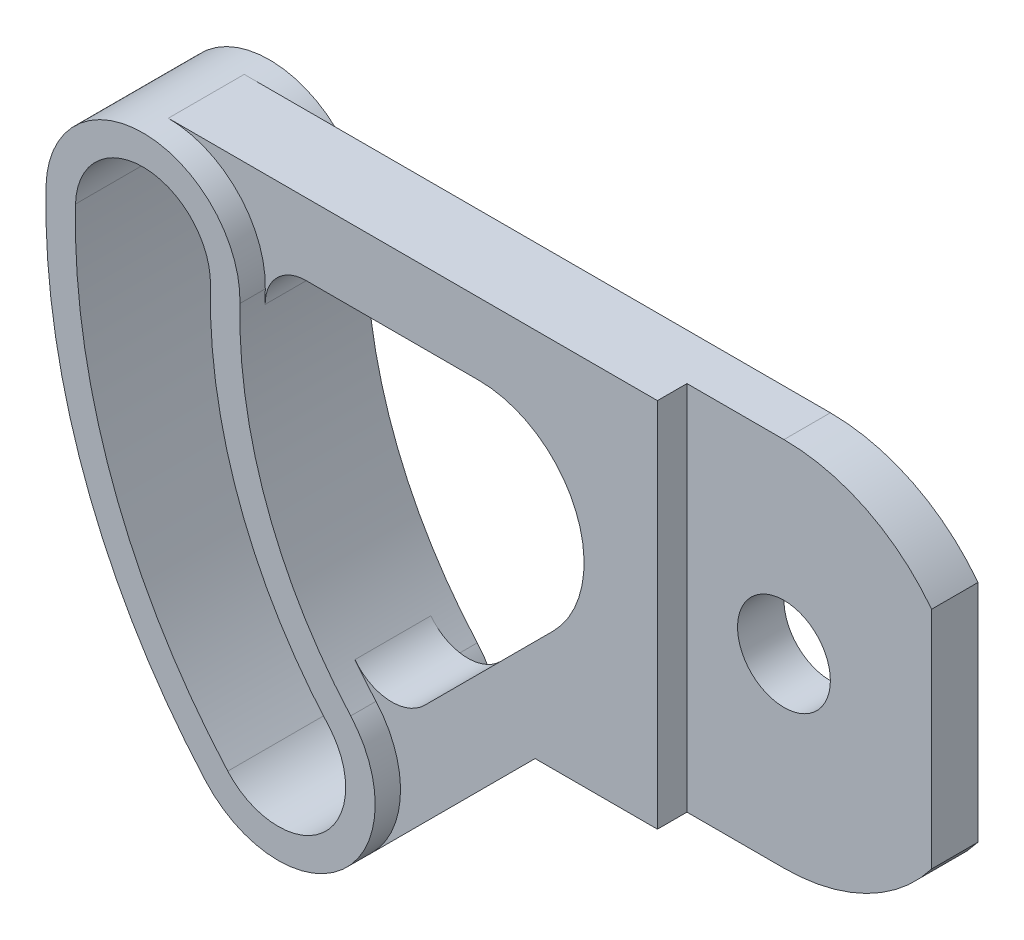
SolidWorks part; units mm, degrees
ref_plane "Front Plane" through (0, 0, 0) normal (0, 0, 1) x (1, 0, 0)
ref_plane "Top Plane" through (0, 0, 0) normal (0, 1, 0) x (1, 0, 0)
ref_plane "Right Plane" through (0, 0, 0) normal (1, 0, 0) x (0, 0, -1)
sketch "Sketch1" plane through (0, 0, 0) normal (0, 0, 1) x (1, 0, 0)
  line L0 (0, -44) -> (-52, -44)
  line L1 (-52, -44) -> (-90.6482, -82.6482)
  line L2 (0, 44) -> (-138.9646, 44)
  line L3 (-23, 44) -> (-23, -44)
  line L4 (35, 26.6646) -> (35, -26.6646)
  line L5 (-65.397, 27) -> (-106.3222, 27)
  line L6 (-47.7193, -15.6777) -> (-78.1904, -46.1488)
  circle A0 centre (0, 0) radius 11
  arc A1 (0, -44) -> (35, -26.6646) centre (0, 0) ccw
  arc A2 (-138.9646, 21) -> (-106.9116, -66.3847) centre (-12, 18) ccw construction
  arc A3 (-161.9581, 21.5433) -> (-124.1004, -81.667) centre (-12, 18) ccw
  arc A4 (-115.971, 20.4567) -> (-89.7229, -51.1025) centre (-12, 18) ccw
  arc A5 (-115.971, 20.4567) -> (-161.9581, 21.5433) centre (-138.9646, 21) ccw
  arc A6 (-124.1004, -81.667) -> (-89.7229, -51.1025) centre (-106.9116, -66.3847) ccw
  arc A7 (-154.9601, 21.378) -> (-118.869, -77.0159) centre (-12, 18) ccw
  arc A8 (-118.869, -77.0159) -> (-94.9543, -55.7536) centre (-106.9116, -66.3847) ccw
  arc A9 (-122.969, 20.622) -> (-94.9543, -55.7536) centre (-12, 18) ccw
  arc A10 (-122.969, 20.622) -> (-154.9601, 21.378) centre (-138.9646, 21) ccw
  arc A11 (-65.397, 27) -> (-47.7193, -15.6777) centre (-65.397, 2) cw
  arc A12 (-106.3222, 27) -> (-115.9973, 17.2554) centre (-106.3222, 17.3247) ccw
  arc A13 (-78.1904, -46.1488) -> (-94.7176, -45.0381) centre (-85.9686, -38.3706) cw
  arc A14 (35, 26.6646) -> (0, 44) centre (0, 0) ccw
  point P12 (-131.2321, -25.7346)
  point P38 (-58.0903, -11.3717)
  point P39 (-83.8076, -37.8936)
  dimension "D1" = 88
  dimension "D3" = 23
  dimension "D6" = 127
  dimension "D9" = 22
  dimension "D11" = 25
  dimension "D13" = 11
  dimension "D14" = 9.6753
  dimension "D2" = 52
  dimension "D4" = 12
  dimension "D5" = 18
  dimension "D8" = 45
  dimension "D10" = 35
  dimension "D12" = 17
  dimension "D15" = 23
  dimension "D16" = 17
  dimension "D7" = 7
extrude "Boss-Extrude1" add sketch "Sketch1" along normal mid plane 30 contours A3 A6 A4 A5 A10 A9 A8 A7 region at (-107.5406, -87.8299, 0)
extrude "Boss-Extrude2" add sketch "Sketch1<3>" along normal mid plane 18 contours L6 A13 A4 A6 L1 L0 L3 L2 A5 A12 L5 A11 region at (-37.5, -42.2828, 0)
sketch "Sketch1<3>" plane through (0, 0, 0) normal (0, 0, 1) x (1, 0, 0) same geometry as "Sketch1"
extrude "Boss-Extrude3" add sketch "Sketch1<4>" along normal mid plane 11 from offset 3.5 contours L4 A14 L2 L3 L0 A1 A0 region at (-11.5, -42.9461, 0) offset against normal yes
sketch "Sketch1<4>" plane through (0, 0, 0) normal (0, 0, 1) x (1, 0, 0) same geometry as "Sketch1"
